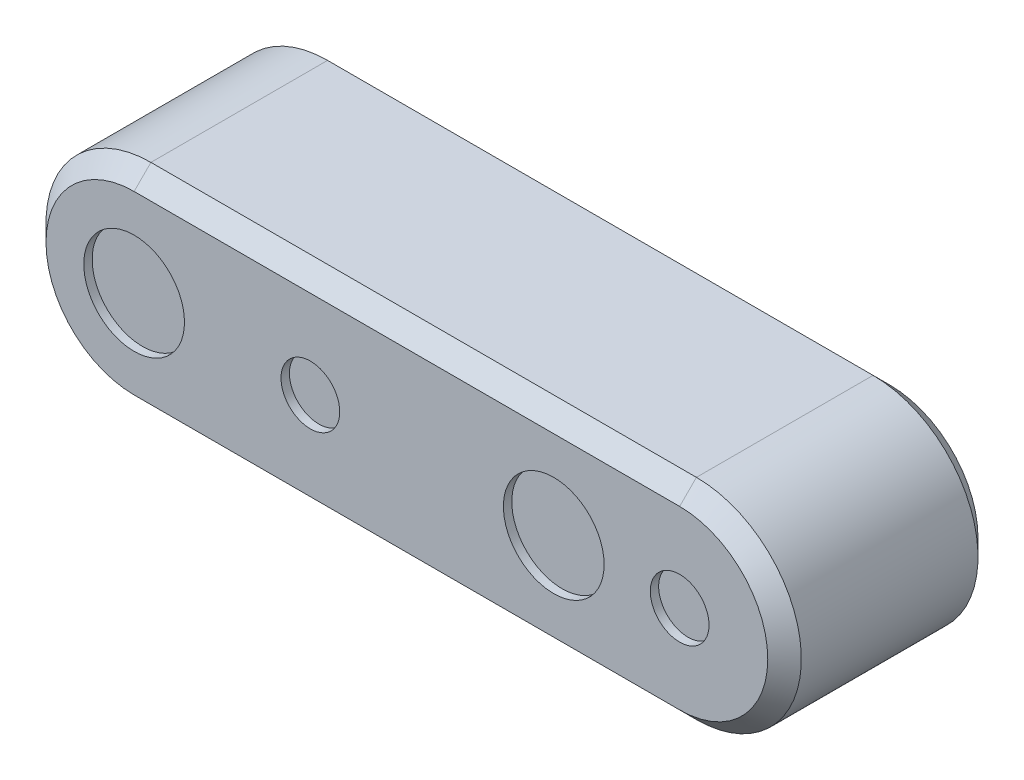
SolidWorks part; units mm, degrees
ref_plane "Front Plane" through (0, 0, 0) normal (0, 0, 1) x (1, 0, 0)
ref_plane "Top Plane" through (0, 0, 0) normal (0, 1, 0) x (1, 0, 0)
ref_plane "Right Plane" through (0, 0, 0) normal (1, 0, 0) x (0, 0, -1)
sketch "Sketch1" plane through (0, 0, 0) normal (0, 0, 1) x (1, 0, 0)
  line L0 (-32.5, 0) -> (32.5, 0) construction
  line L1 (-32.5, 12.5) -> (32.5, 12.5)
  line L2 (-32.5, -12.5) -> (32.5, -12.5)
  arc A0 (-32.5, 12.5) -> (-32.5, -12.5) centre (-32.5, 0) ccw
  arc A1 (32.5, -12.5) -> (32.5, 12.5) centre (32.5, 0) ccw
  point P2 (0, 0)
  dimension "D2" = 90
  dimension "D1" = 25
extrude "Boss-Extrude1" add sketch "Sketch1" along normal blind 12.525 and the other way blind 12.525
sketch "Sketch2" plane through (0, 0, 12.525) normal (0, 0, 1) x (1, 0, 0)
  line L0 (-32.5, 0) -> (32.5, 0) construction
  circle A0 centre (-32.5, 0) radius 6
  circle A1 centre (-11.5, 0) radius 3.5
  circle A2 centre (17.5, 0) radius 6
  circle A3 centre (32.5, 0) radius 3.5
  dimension "D1" = 12
  dimension "D2" = 7
  dimension "D3" = 50
  dimension "D4" = 29
  dimension "D5" = 15
  dimension "D6" = 17.5
extrude "Cut-Extrude1" cut sketch "Sketch2" against normal blind 1
sketch "Sketch3" plane through (0, 0, -12.525) normal (0, 0, -1) x (-1, 0, 0)
  line L0 (-22.5, 0) -> (22.5, 0) construction
  circle A0 centre (22.5, 0) radius 1.6
  circle A1 centre (-22.5, 0) radius 1.6
  point P4 (0, 0)
  dimension "D1" = 3.2
  dimension "D2" = 45
extrude "Cut-Extrude2" cut sketch "Sketch3" against normal blind 3
chamfer "Chamfer1" distance 2 angle 45 8 edges at (0, -12.5, -12.525) (45, 0, -12.525) (-45, 0, -12.525) (0, 12.5, -12.525) (0, -12.5, 12.525) (45, 0, 12.525) (-45, 0, 12.525) (0, 12.5, 12.525)
sketch "Sketch4" plane through (0, 0, 12.525) normal (0, 0, 1) x (1, 0, 0)
  line L0 (-32.5, 0) -> (17.5, 0) construction
  circle A0 centre (-32.5, 0) radius 6 construction
  circle A1 centre (17.5, 0) radius 6 construction
  circle A2 centre (-32.5, 0) radius 6 construction
  circle A3 centre (17.5, 0) radius 6 construction
  point P6 (-7.5, 0)
ref_plane "Plane1" through (-7.5, 0, 0) normal (1, 0, 0) x (0, 0, -1)
